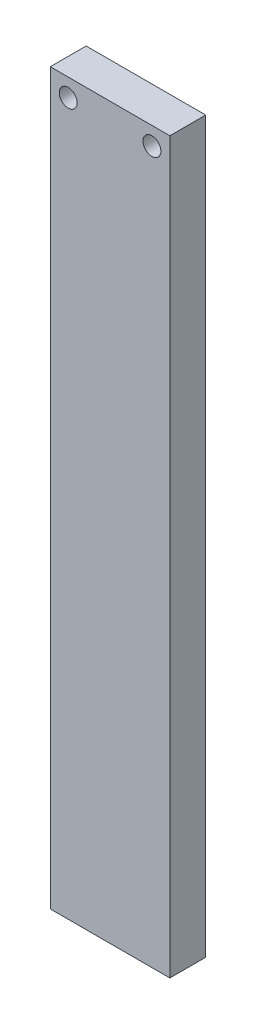
SolidWorks part; units mm, degrees
ref_plane "Plan de face" through (0, 0, 0) normal (0, 0, 1) x (1, 0, 0)
ref_plane "Plan de dessus" through (0, 0, 0) normal (0, 1, 0) x (1, 0, 0)
ref_plane "Plan de droite" through (0, 0, 0) normal (1, 0, 0) x (0, 0, -1)
sketch "Esquisse1" plane through (0, 0, 0) normal (0, 0, 1) x (1, 0, 0)
  line L1 (-10, 84) -> (10, 84)
  line L2 (-10, 84) -> (-10, -38)
  line L3 (-10, -38) -> (10, -38)
  line L4 (10, 84) -> (10, -38)
  dimension "D1" = 122
  dimension "D2" = 20
  dimension "D3" = 10
  dimension "D4" = 38
extrude "Boss.-Extru.1" add sketch "Esquisse1" along normal blind 6
sketch "Esquisse2" plane through (0, 0, 6) normal (0, 0, 1) x (1, 0, 0)
  line L0 (-21.2963, 81) -> (25.2376, 81) construction
  line L1 (10, 84) -> (-10, 84) construction
  line L2 (-10, 84) -> (-10, -38) construction
  line L3 (10, -38) -> (10, 84) construction
  circle A0 centre (-7, 81) radius 1.5
  circle A1 centre (7, 81) radius 1.5
  dimension "D1" = 3
  dimension "D2" = 3
  dimension "D4" = 3
  dimension "D5" = 3
  dimension "D3" = 3
extrude "Enlèv. mat.-Extru.1" cut sketch "Esquisse2" against normal blind 6
equation "\"D3@Esquisse1\"=\"D2@Esquisse1\"/2"
equation "\"D4@Esquisse1\"=\"D1@Esquisse1\"/2"
